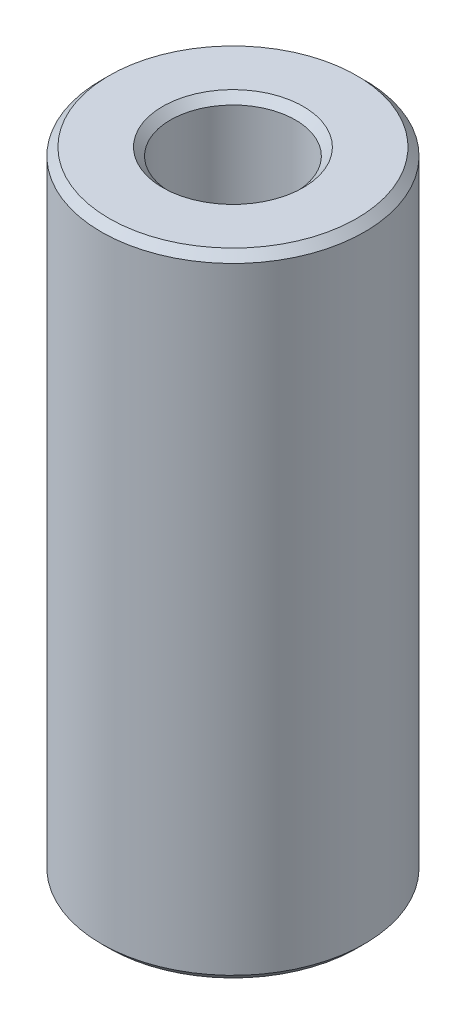
SolidWorks part; units mm, degrees
ref_plane "Front Plane" through (0, 0, 0) normal (0, 0, 1) x (1, 0, 0)
ref_plane "Top Plane" through (0, 0, 0) normal (0, 1, 0) x (1, 0, 0)
ref_plane "Right Plane" through (0, 0, 0) normal (1, 0, 0) x (0, 0, -1)
sketch "Sketch1" plane through (0, 0, 0) normal (0, 1, 0) x (1, 0, 0)
  circle A0 centre (0, 0) radius 52.5
  dimension "SLEEVE_OD" = 105
extrude "Boss-Extrude1" add sketch "Sketch1" along normal blind 252.1632
sketch "Sketch2" plane through (0, 0, 0) normal (0, 1, 0) x (1, 0, 0)
  circle A0 centre (0, 0) radius 24.9472
  dimension "BORE_D" = 49.8944
extrude "Cut-Extrude1" cut sketch "Sketch2" along normal through all
chamfer "Chamfer1" distance 3.1158 angle 45 4 edges at (0, 252.1632, 24.9472) (0, 0, 24.9472) (0, 0, 52.5) (0, 252.1632, 52.5)
